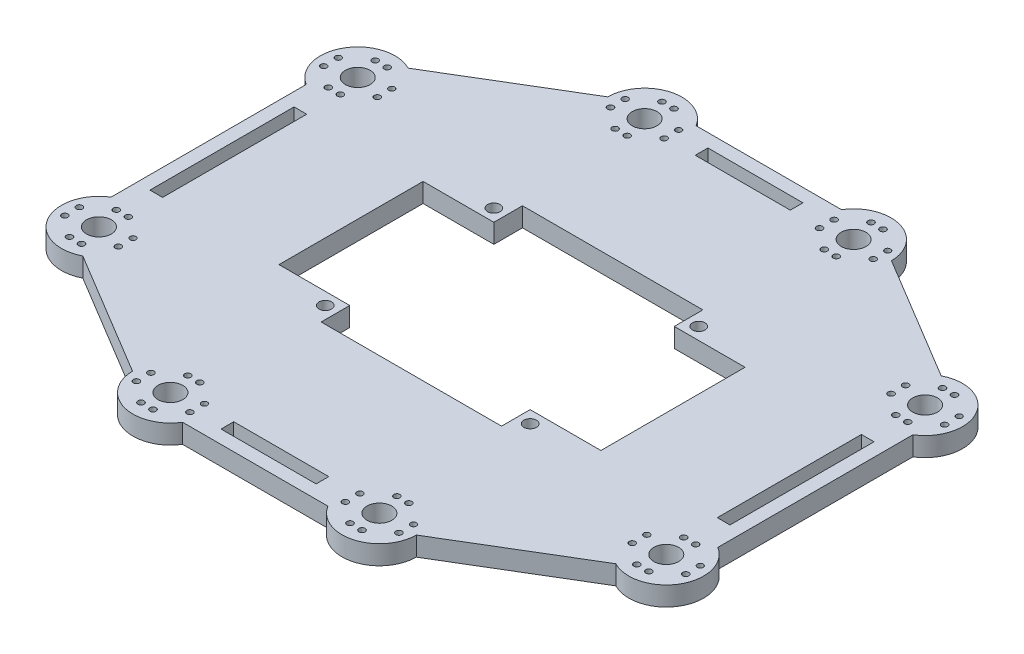
SolidWorks part; units mm, degrees
ref_plane "Front Plane" through (0, 0, 0) normal (0, 0, 1) x (1, 0, 0)
ref_plane "Top Plane" through (0, 0, 0) normal (0, 1, 0) x (1, 0, 0)
ref_plane "Right Plane" through (0, 0, 0) normal (1, 0, 0) x (0, 0, -1)
sketch "Sketch1" plane through (0, 0, 0) normal (0, 1, 0) x (1, 0, 0)
  line L0 (-75.3872, 32.1628) -> (-75.3872, -32.1628)
  line L1 (75.3872, 32.1628) -> (75.3872, -32.1628)
  line L2 (-25.9715, -63.8111) -> (25.9715, -63.8111)
  line L3 (-25.9715, 63.8111) -> (25.9715, 63.8111)
  line L4 (-73.0163, 36.3537) -> (-28.4901, 63.1126)
  line L5 (28.4901, 63.1126) -> (73.0163, 36.3537)
  line L6 (-73.0163, -36.3537) -> (-28.4901, -63.1126)
  line L7 (28.4901, -63.1126) -> (73.0163, -36.3537)
  line L8 (-73.0163, 36.3537) -> (-75.3872, 32.1628)
  line L9 (-75.3872, -32.1628) -> (-73.0163, -36.3537)
  line L10 (-28.4901, -63.1126) -> (-25.9715, -63.8111)
  line L11 (25.9715, -63.8111) -> (28.4901, -63.1126)
  line L12 (73.0163, -36.3537) -> (75.3872, -32.1628)
  line L13 (75.3872, 32.1628) -> (73.0163, 36.3537)
  line L14 (28.4901, 63.1126) -> (25.9715, 63.8111)
  line L15 (-25.9715, 63.8111) -> (-28.4901, 63.1126)
  line L16 (-40.005, 17.907) -> (-40.005, -17.907)
  line L17 (40.005, 17.907) -> (40.005, -17.907)
  line L18 (-22.4155, -25.019) -> (22.4155, -25.019)
  line L19 (-22.4155, 25.019) -> (22.4155, 25.019)
  line L20 (-40.005, 17.907) -> (-22.4155, 17.907)
  line L21 (40.005, 17.907) -> (22.4155, 17.907)
  line L22 (40.005, -17.907) -> (22.4155, -17.907)
  line L23 (-40.005, -17.907) -> (-22.4155, -17.907)
  line L24 (-22.4155, 25.019) -> (-22.4155, 17.907)
  line L25 (22.4155, 25.019) -> (22.4155, 17.907)
  line L26 (22.4155, -17.907) -> (22.4155, -25.019)
  line L27 (-22.4155, -17.907) -> (-22.4155, -25.019)
  line L29 (-68.9229, -17.907) -> (-72.0725, -17.907)
  line L30 (-68.9229, -17.907) -> (-68.9229, 17.907)
  line L31 (-68.9229, 17.907) -> (-72.0725, 17.907)
  line L32 (-72.0725, -17.907) -> (-72.0725, 17.907)
  line L33 (68.9229, 17.907) -> (72.0725, 17.907)
  line L34 (68.9229, 17.907) -> (68.9229, -17.907)
  line L35 (68.9229, -17.907) -> (72.0725, -17.907)
  line L36 (72.0725, 17.907) -> (72.0725, -17.907)
  line L37 (-11.811, -60.4964) -> (11.811, -60.4964)
  line L38 (-11.811, -60.4964) -> (-11.811, -57.3469)
  line L39 (-11.811, -57.3469) -> (11.811, -57.3469)
  line L40 (11.811, -60.4964) -> (11.811, -57.3469)
  line L41 (-11.811, 60.4964) -> (11.811, 60.4964)
  line L42 (-11.811, 60.4964) -> (-11.811, 57.3469)
  line L43 (-11.811, 57.3469) -> (11.811, 57.3469)
  line L44 (11.811, 60.4964) -> (11.811, 57.3469)
  circle A0 centre (25.9715, -58.9216) radius 9.3027
  circle A1 centre (25.9715, -58.9216) radius 3.0798
  circle A2 centre (27.4637, -53.105) radius 0.762
  circle A3 centre (24.4792, -53.105) radius 0.762
  circle A4 centre (24.4792, -64.7382) radius 0.762
  circle A5 centre (27.4637, -64.7382) radius 0.762
  circle A6 centre (19.3167, -57.1119) radius 0.762
  circle A7 centre (19.3167, -60.7314) radius 0.762
  circle A8 centre (32.6263, -57.1119) radius 0.7341
  circle A10 centre (32.6263, -60.7314) radius 0.762
  circle A11 centre (-63.8429, 30.353) radius 0.762
  circle A12 centre (-77.1525, 30.353) radius 0.762
  circle A13 centre (-71.9899, 26.3462) radius 0.762
  circle A14 centre (-77.1525, 33.9725) radius 0.762
  circle A15 centre (-70.4977, 32.1628) radius 9.3028
  circle A16 centre (-70.4977, 32.1628) radius 3.0798
  circle A17 centre (-69.0054, 26.3462) radius 0.762
  circle A18 centre (-71.9899, 37.9794) radius 0.762
  circle A19 centre (-63.8429, 33.9725) radius 0.7341
  circle A20 centre (-69.0054, 37.9794) radius 0.762
  circle A21 centre (-70.4977, -32.1628) radius 9.3028
  circle A22 centre (-70.4977, -32.1628) radius 3.0798
  circle A23 centre (-69.0054, -26.3462) radius 0.762
  circle A24 centre (-71.9899, -26.3462) radius 0.762
  circle A25 centre (-71.9899, -37.9794) radius 0.762
  circle A26 centre (-69.0054, -37.9794) radius 0.762
  circle A27 centre (-77.1525, -30.353) radius 0.762
  circle A28 centre (-77.1525, -33.9725) radius 0.762
  circle A29 centre (-63.8429, -30.353) radius 0.7341
  circle A30 centre (-63.8429, -33.9725) radius 0.762
  circle A31 centre (70.4977, 32.1628) radius 9.3027
  circle A32 centre (70.4977, 32.1628) radius 3.0798
  circle A33 centre (71.9899, 37.9794) radius 0.762
  circle A34 centre (69.0054, 37.9794) radius 0.762
  circle A35 centre (69.0054, 26.3462) radius 0.762
  circle A36 centre (71.9899, 26.3462) radius 0.762
  circle A37 centre (63.8429, 33.9725) radius 0.762
  circle A38 centre (63.8429, 30.353) radius 0.762
  circle A39 centre (77.1525, 33.9725) radius 0.7341
  circle A40 centre (77.1525, 30.353) radius 0.762
  circle A41 centre (70.4977, -32.1628) radius 9.3027
  circle A42 centre (70.4977, -32.1628) radius 3.0798
  circle A43 centre (71.99, -26.3462) radius 0.762
  circle A44 centre (69.0055, -26.3462) radius 0.762
  circle A45 centre (69.0055, -37.9794) radius 0.762
  circle A46 centre (71.99, -37.9794) radius 0.762
  circle A47 centre (63.8429, -30.353) radius 0.762
  circle A48 centre (63.8429, -33.9725) radius 0.762
  circle A49 centre (77.1525, -30.353) radius 0.7341
  circle A50 centre (77.1525, -33.9725) radius 0.762
  circle A51 centre (25.9715, 58.9216) radius 9.3027
  circle A52 centre (25.9715, 58.9216) radius 3.0797
  circle A53 centre (27.4637, 64.7382) radius 0.762
  circle A54 centre (24.4792, 64.7382) radius 0.762
  circle A55 centre (24.4792, 53.105) radius 0.762
  circle A56 centre (27.4637, 53.105) radius 0.762
  circle A57 centre (19.3167, 60.7314) radius 0.762
  circle A58 centre (19.3167, 57.1119) radius 0.762
  circle A59 centre (32.6263, 60.7314) radius 0.7341
  circle A60 centre (32.6263, 57.1119) radius 0.762
  circle A61 centre (-25.9715, 58.9216) radius 9.3027
  circle A62 centre (-25.9715, 58.9216) radius 3.0797
  circle A63 centre (-24.4792, 64.7382) radius 0.762
  circle A64 centre (-27.4637, 64.7382) radius 0.762
  circle A65 centre (-27.4637, 53.105) radius 0.762
  circle A66 centre (-24.4792, 53.105) radius 0.762
  circle A67 centre (-32.6263, 60.7314) radius 0.762
  circle A68 centre (-32.6263, 57.1119) radius 0.762
  circle A69 centre (-19.3167, 60.7314) radius 0.7341
  circle A70 centre (-19.3167, 57.1119) radius 0.762
  circle A71 centre (-25.9715, -58.9216) radius 9.3027
  circle A72 centre (-25.9715, -58.9216) radius 3.0797
  circle A73 centre (-24.4792, -53.105) radius 0.762
  circle A74 centre (-27.4637, -53.105) radius 0.762
  circle A75 centre (-27.4637, -64.7382) radius 0.762
  circle A76 centre (-24.4792, -64.7382) radius 0.762
  circle A77 centre (-32.6263, -57.1119) radius 0.762
  circle A78 centre (-32.6263, -60.7314) radius 0.762
  circle A79 centre (-19.3167, -57.1119) radius 0.7341
  circle A80 centre (-19.3167, -60.7314) radius 0.762
  circle A81 centre (-25.4572, 20.9487) radius 1.5558
  circle A82 centre (25.4572, 20.9487) radius 1.5557
  circle A83 centre (25.4572, -20.9487) radius 1.5557
  circle A84 centre (-25.4572, -20.9487) radius 1.5557
extrude "Boss-Extrude1" add sketch "Sketch1" along normal blind 4.7625 contours L15 L4 L8 L0 L9 L6 L10 L2 L11 L7 L12 L1 L13 L5 L14 L3 | A21 | A71 | A0 | A41 | A31 | A51 | A61 | A15
extrude "Cut-Extrude2" cut sketch "Sketch1<6>" against normal mid plane 9.525 contours L23 L27 L18 L26 L22 L17 L21 L25 L19 L24 L20 L16 | A83 | A82 | A84 | A81 | A46 | A45 | A50 | A49 | A43 | A44 | A42 | A47 | A48 | L34 L35 L36 L33 | A40 | A39 | A36 | A35 | A32 | A38 | A37 | A33 | A34 | A60 | A59 | A53 | A54 | A57 | A58 | A55 | A56 | A52 | L43 L44 L41 L42 | A70 | A69 | A63 | A64 | A67 | A68 | A65 | A66 | A62 | A20 | A18 | A14 | A12 | A16 | A13 | A17 | A11 | A19 | L32 L31 L30 L29 | A23 | A24 | A27 | A28 | A25 | A26 | A30 | A29 | A22 | A74 | A73 | A79 | A80 | A76 | A75 | A78 | A77 | A72 | L38 L39 L40 L37 | A8 | A10 | A5 | A4 | A7 | A6 | A3 | A2 | A1 region at (0, 0, 0)
sketch "Sketch1<6>" plane through (0, 0, 0) normal (0, 1, 0) x (1, 0, 0) same geometry as "Sketch1"
